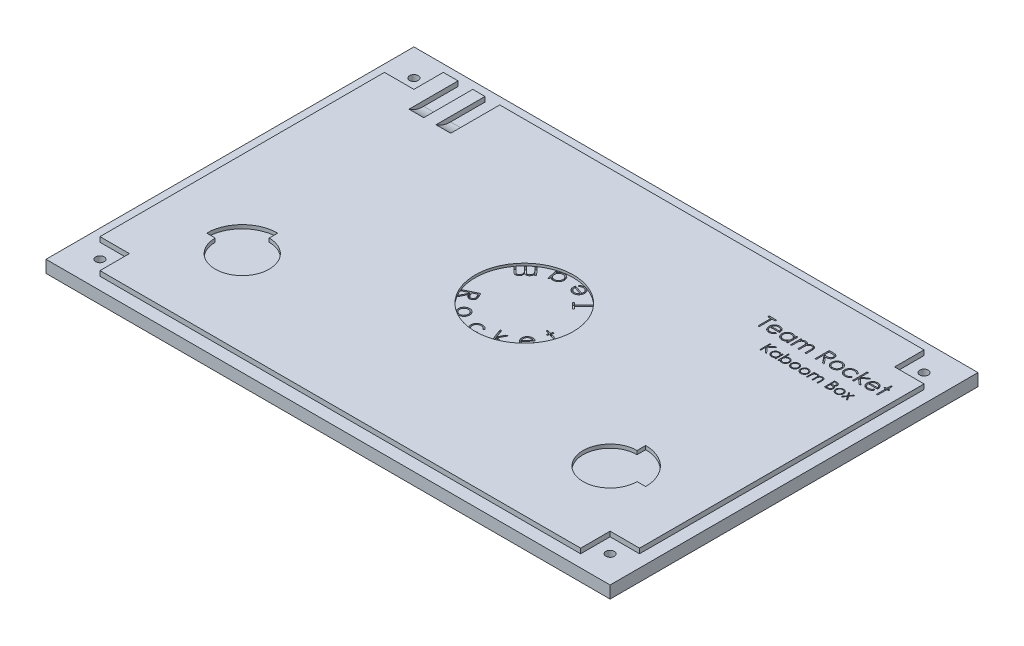
SolidWorks part; units mm, degrees
ref_plane "Front Plane" through (0, 0, 0) normal (0, 0, 1) x (1, 0, 0)
ref_plane "Top Plane" through (0, 0, 0) normal (0, 1, 0) x (1, 0, 0)
ref_plane "Right Plane" through (0, 0, 0) normal (1, 0, 0) x (0, 0, -1)
sketch "Sketch1" plane through (0, 0, 0) normal (0, 1, 0) x (1, 0, 0)
  line L0 (0, 91.3094) -> (0, -103.2904) construction
  line L1 (-173.7239, 0) -> (176.9914, 0) construction
  line L3 (-115, -75) -> (115, -75)
  line L4 (-115, -75) -> (-115, 75)
  line L5 (-115, 75) -> (115, 75)
  line L6 (115, -75) -> (115, 75)
  line L7 (-115, -75) -> (115, 75) construction
  line L8 (-115, 75) -> (115, -75) construction
  point P5 (0, 0)
  dimension "D1" = 150
  dimension "D2" = 230
extrude "Boss-Extrude1" add sketch "Sketch1" along normal blind 7
sketch "Sketch2" plane through (0, 7, 0) normal (0, 1, 0) x (1, 0, 0)
  line L8 (110, -70) -> (110, 70)
  line L9 (110, 70) -> (-110, 70)
  line L10 (-110, 70) -> (-110, -70)
  line L11 (-110, -70) -> (110, -70)
  line L12 (110, -70) -> (110, 70)
  line L13 (110, 70) -> (-110, 70)
  line L14 (-110, 70) -> (-110, -70)
  line L15 (-110, -70) -> (110, -70)
  line M5 (115, -75) -> (115, 75)
  line M6 (115, 75) -> (-115, 75)
  line M7 (-115, 75) -> (-115, -75)
  line M8 (-115, -75) -> (115, -75)
  dimension "D1" = 5
sketch "Sketch3" plane through (0, 7, 0) normal (0, 1, 0) x (1, 0, 0)
  line L0 (0, 87.5018) -> (0, -99.4565) construction
  line L1 (-139.3055, 0) -> (141.6301, 0) construction
  line L2 (-139.3055, -35) -> (150.5961, -35) construction
  line L3 (-75, -35) -> (-75, -4.8004) construction
  line L4 (-143.9546, 5) -> (150.5961, 5) construction
  line L5 (-75, -24) -> (-75, -20.5)
  line L6 (-89.5, -35) -> (-86, -35)
  circle A0 centre (0, 5) radius 20
  circle A1 centre (-75, -35) radius 11
  circle A2 centre (75, -35) radius 11
  circle A3 centre (-75, -35) radius 14.5
  point P11 (0, 5)
  dimension "D3" = 80
  dimension "D4" = 22
  dimension "D5" = 29
  dimension "D6" = 40
  dimension "D1" = 40
  dimension "D2" = 40
sketch "Sketch7" plane through (0, 7, 0) normal (0, 1, 0) x (1, 0, 0)
  line L0 (0, 98.647) -> (0, -123.6095) construction
  line L1 (-75, -35) -> (73.1452, -35) construction
  line L2 (-75, -35) -> (0, 5) construction
  line L3 (-139.3055, -35) -> (150.5961, -35) construction
  circle A0 centre (-75, -35) radius 11
  circle A1 centre (75, -35) radius 11
  dimension "D1" = 28.072
  dimension "D2" = 85
extrude "Cut-Extrude2" cut sketch "Sketch2" against normal blind 2 contours L15 L14 L13 L12 M8 M5 M6 M7 region at (0, 7, 72.2541)
extrude "Cut-Extrude3" cut sketch "Sketch3" against normal blind 1 contours A0
extrude "Cut-Extrude5" cut sketch "Sketch3<4>" against normal blind 1.5 contours L5 A3 L6 A1 | A1 region at (-83.1679, 7, 26.8321)
sketch "Sketch3<4>" plane through (0, 7, 0) normal (0, 1, 0) x (1, 0, 0) same geometry as "Sketch3"
mirror "Mirror1" about plane through (0, 0, 0) normal (1, 0, 0) of "Cut-Extrude5"
sketch "Sketch8" plane through (0, 7, 0) normal (0, 1, 0) x (1, 0, 0)
  line L0 (-104, -58) -> (-104, -70) construction
  line L1 (-110, -70) -> (-98, -70)
  line L2 (-110, -70) -> (-110, -58)
  line L3 (-110, -58) -> (-98, -58)
  line L4 (-98, -70) -> (-98, -58)
  line L5 (-110, -64) -> (-98, -64) construction
  circle A0 centre (-104, -64) radius 1.75
  dimension "D3" = 3.5
  dimension "D1" = 12
  dimension "D2" = 12
extrude "Cut-Extrude6" cut sketch "Sketch8" against normal up to surface (2 mm away) up to face at (0, 5, 0)
sketch "Sketch9" plane through (0, 7, 0) normal (0, 1, 0) x (1, 0, 0)
  circle A0 centre (-104, -64) radius 1.75
  dimension "D1" = 3.5
extrude "Cut-Extrude7" cut sketch "Sketch9" against normal through all contours A0
mirror "Mirror2" about plane through (0, 0, 0) normal (1, 0, 0) of "Cut-Extrude7", "Cut-Extrude6"
mirror "Mirror3" about plane through (0, 0, 0) normal (0, 0, 1) of "Cut-Extrude7", "Mirror2", "Cut-Extrude6"
sketch "Sketch10" plane through (0, 7, 0) normal (0, 1, 0) x (1, 0, 0)
  text T0 "  Team  Rocket" font "Century Gothic" height 6
extrude "Cut-Extrude8" cut sketch "Sketch10" against normal blind 2.1
sketch "Sketch13" plane through (0, 7, 0) normal (0, 1, 0) x (1, 0, 0)
  line L0 (110, 44.6426) -> (38.0739, 44.6426) construction
  line L2 (110, -58) -> (110, 58) construction
  text T0 "Team Rocket  " font "Century Gothic" height in points 22
  text T1 "\r\nKaboom Box      " font "Century Gothic" height in points 16
extrude "Cut-Extrude11" cut sketch "Sketch13" against normal blind 0.8
sketch "Sketch14" plane through (0, 7, 0) normal (0, 1, 0) x (1, 0, 0)
  line L0 (-75, 70) -> (-75, 50)
  line L1 (98, 70) -> (-98, 70) construction
  line L4 (-86, 70) -> (-86, 50)
  line L5 (-86, 50) -> (-92, 50)
  line L6 (-92, 50) -> (-92, 70)
  line L7 (-92, 70) -> (-86, 70)
  line L9 (-110, 58) -> (-110, -58) construction
  line L10 (-75, 50) -> (-81, 50)
  line L11 (-81, 50) -> (-81, 70)
  line L12 (-81, 70) -> (-75, 70)
  dimension "D1" = 35
  dimension "D2" = 17
  dimension "D3" = 6
  dimension "D4" = 6
  dimension "D5" = 20
extrude "Cut-Extrude12" cut sketch "Sketch14" against normal blind 2
fillet "Fillet5" radius 10 2 edges at (-78, 5, -50) (-89, 5, -50)
